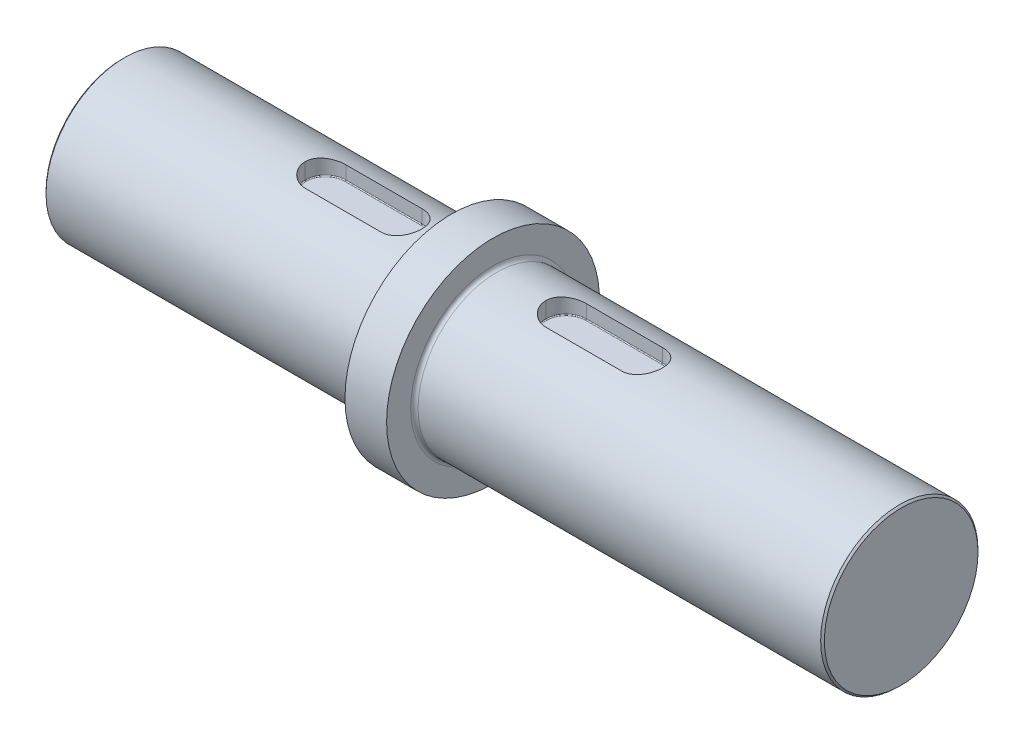
SolidWorks part; units mm, degrees
ref_plane "Piano frontale" through (0, 0, 0) normal (0, 0, 1) x (1, 0, 0)
ref_plane "Piano superiore" through (0, 0, 0) normal (0, 1, 0) x (1, 0, 0)
ref_plane "Piano destro" through (0, 0, 0) normal (1, 0, 0) x (0, 0, -1)
sketch "Schizzo1" plane through (0, 0, 0) normal (0, 0, 1) x (1, 0, 0)
  line L0 (-146.8568, 0) -> (411.199, 0) construction
  line L1 (0, 0) -> (0, 42.5)
  line L2 (0, 42.5) -> (165.5, 42.5)
  line L3 (165.5, 42.5) -> (165.5, 57.5)
  line L4 (165.5, 57.5) -> (188, 57.5)
  line L5 (188, 57.5) -> (188, 42.5)
  line L6 (188, 42.5) -> (378.5, 42.5)
  line L7 (378.5, 42.5) -> (378.5, 0)
  line L8 (378.5, 0) -> (0, 0)
  dimension "D1" = 378.5
  dimension "D2" = 85
  dimension "D3" = 165.5
  dimension "D4" = 22.5
  dimension "D5" = 15
revolve "Rivoluzione1" add sketch "Schizzo1" angle 360 about L0
sketch "Schizzo2" plane through (0, 0, 0) normal (0, 0, 1) x (1, 0, 0)
  line L0 (165.5, 42.5) -> (0, 42.5) construction
  line L1 (86.5, 47.5) -> (149.5, 47.5)
  line L2 (86.5, 47.5) -> (86.5, 33.5)
  line L3 (86.5, 33.5) -> (149.5, 33.5)
  line L4 (149.5, 47.5) -> (149.5, 33.5)
  line L5 (216.5, 47.5) -> (279.5, 47.5)
  line L6 (216.5, 47.5) -> (216.5, 33.5)
  line L7 (216.5, 33.5) -> (279.5, 33.5)
  line L8 (279.5, 47.5) -> (279.5, 33.5)
  line L9 (378.5, 42.5) -> (188, 42.5) construction
  line L10 (118, 94.3393) -> (118, 0) construction
  line L11 (248, 110.2039) -> (248, -13.5399) construction
  line L12 (176.75, 83.2341) -> (176.75, -8.7805) construction
  line L13 (165.5, 57.5) -> (165.5, -57.5) construction
  line L14 (188, -57.5) -> (188, 57.5) construction
  line L15 (188, -42.5) -> (188, 42.5) construction
  line L18 (378.5, -42.5) -> (378.5, 42.5) construction
  dimension "D1" = 63
  dimension "D2" = 63
  dimension "D3" = 14
  dimension "D4" = 14
  dimension "D5" = 9
  dimension "D6" = 9
  dimension "D7" = 47.5
  dimension "D8" = 60
extrude "Taglio-Estrusione1" cut sketch "Schizzo2" against normal blind 11 and the other way blind 11
fillet "Raccordo1" radius 0.5 8 edges at (216.5, 33.5, 0) (248, 33.5, 11) (279.5, 33.5, 0) (149.5, 33.5, 0) (118, 33.5, 11) (86.5, 33.5, 0) (118, 33.5, -11) (248, 33.5, -11)
fillet "Raccordo2" radius 11 16 edges at (279.3536, 33.6464, -10.8536) (279.3536, 33.6464, 10.8536) (216.6464, 33.6464, 10.8536) (216.6464, 33.6464, -10.8536) (149.3536, 33.6464, 10.8536) (149.3536, 33.6464, -10.8536) (86.6464, 33.6464, 10.8536) (86.6464, 33.6464, -10.8536) (86.5, 37.5259, -11) (86.5, 37.5259, 11) (149.5, 37.5259, -11) (149.5, 37.5259, 11) (216.5, 37.5259, -11) (216.5, 37.5259, 11) (279.5, 37.5259, 11) (279.5, 37.5259, -11)
sketch "Schizzo3" plane through (378.5, 0, 0) normal (1, 0, 0) x (0, 0, -1)
  circle A0 centre (0, 0) radius 42.5
  circle A1 centre (0, 0) radius 42.5 construction
extrude "Estrusione-Estrusione1" add sketch "Schizzo3" along normal blind 30
sketch "Schizzo4" plane through (0, 0, 0) normal (-1, 0, 0) x (0, 0, 1)
  circle A0 centre (0, 0) radius 42.5
  circle A1 centre (0, 0) radius 42.5 construction
extrude "Estrusione-Estrusione2" add sketch "Schizzo4" along normal blind 12
fillet "Raccordo3" radius 2 2 edges at (165.5, 0, 42.5) (188, 0, 42.5)
chamfer "Smusso1" distance 1 angle 45 2 edges at (408.5, 0, -42.5) (-12, 0, 42.5)
